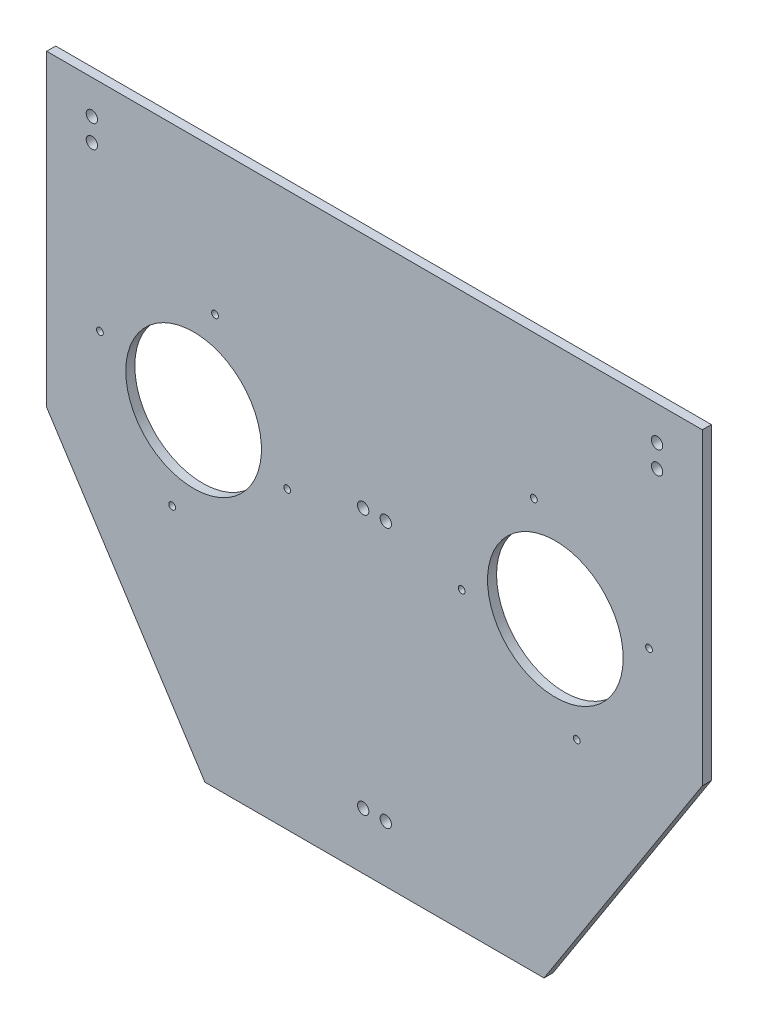
SolidWorks part; units mm, degrees
ref_plane "Front Plane" through (0, 0, 0) normal (0, 0, 1) x (1, 0, 0)
ref_plane "Top Plane" through (0, 0, 0) normal (0, 1, 0) x (1, 0, 0)
ref_plane "Right Plane" through (0, 0, 0) normal (1, 0, 0) x (0, 0, -1)
sketch "Sketch1" plane through (0, 0, 0) normal (0, 0, 1) x (1, 0, 0)
  line L0 (-125, 100) -> (125, 100) construction
  line L1 (-125, 0) -> (125, 0) construction
  line L2 (-145, -16.3871) -> (-75, -125)
  line L3 (-75, -125) -> (75, -125)
  line L4 (75, -125) -> (145, -16.3871)
  line L5 (-125, 105) -> (-125, 95) construction
  line L6 (0, -125) -> (0, 100) construction
  line L7 (-145, 120) -> (145, 120)
  line L8 (145, 120) -> (145, -16.3871)
  line L11 (-145, -16.3871) -> (-145, 120)
  line L12 (125, 105) -> (125, 95) construction
  line L13 (-5, -100) -> (5, -100) construction
  circle A0 centre (-125, 100) radius 12.5 construction
  circle A10 centre (-125, 0) radius 12.5 construction
  circle A11 centre (125, 0) radius 12.5 construction
  circle A12 centre (-125, 0) radius 17.5 construction
  circle A13 centre (-125, 100) radius 17.5 construction
  circle A25 centre (-125, 95) radius 2.5
  circle A26 centre (-125, 105) radius 2.5
  circle A27 centre (125, 95) radius 2.5
  circle A28 centre (125, 105) radius 2.5
  circle A29 centre (5, -100) radius 2.5
  circle A30 centre (-5, -100) radius 2.5
  point P12 (0, 100)
  point P15 (0, -100)
  point P27 (-145, -22.8851)
  point P29 (-145, -16.3871)
  point P45 (0, 120)
  dimension "D1" = 25
  dimension "D2" = 5
  dimension "D4" = 100
  dimension "D6" = 5
  dimension "D11" = 20
  dimension "D12" = 20
  dimension "D7" = 10
  dimension "D8" = 250
  dimension "D3" = 25
  dimension "D5" = 100
  dimension "D9" = 150
extrude "Boss-Extrude1" add sketch "Sketch1" along normal blind 4
sketch "Sketch2" plane through (0, 0, 4) normal (0, 0, 1) x (1, 0, 0)
  line L0 (121.4264, 24.4924) -> (38.5736, 5.5076) construction
  line L1 (89.4924, -26.4264) -> (70.5076, 56.4264) construction
  line L2 (0, 0) -> (0, 96.4486) construction
  line L3 (145, 120) -> (-145, 120) construction
  line L4 (-145, 120) -> (-145, -16.3871) construction
  line L5 (-80, 15) -> (80, 15) construction
  line L6 (-5, 15) -> (5, 15) construction
  circle A0 centre (80, 15) radius 42.5 construction
  circle A1 centre (38.5736, 5.5076) radius 1.5
  circle A2 centre (70.5076, 56.4264) radius 1.5
  circle A3 centre (121.4264, 24.4924) radius 1.5
  circle A4 centre (89.4924, -26.4264) radius 1.5
  circle A5 centre (80, 15) radius 30
  circle A6 centre (-38.5736, 5.5076) radius 1.5
  circle A7 centre (-70.5076, 56.4264) radius 1.5
  circle A8 centre (-89.4924, -26.4264) radius 1.5
  circle A9 centre (-121.4264, 24.4924) radius 1.5
  circle A10 centre (-80, 15) radius 42.5 construction
  circle A11 centre (-80, 15) radius 30
  circle A12 centre (-80, 15) radius 47.5 construction
  circle A15 centre (-5, 15) radius 2.5
  circle A16 centre (5, 15) radius 2.5
  point P6 (80, 15)
  point P27 (-80, 15)
  point P30 (0, 15)
  dimension "D1" = 85
  dimension "D2" = 3
  dimension "D3" = 60
  dimension "D4" = 95
  dimension "D5" = 5
  dimension "D6" = 105
  dimension "D7" = 65
  dimension "D8" = 10
extrude "Cut-Extrude1" cut sketch "Sketch2" against normal blind 10
equation "\"D1@Sketch1\" = \"cf_tube_outer_diameter\""
equation "\"mid_plate_mid_to_top\" = 100mm"
equation "\"mid_plate_mid_to_bottom\" = 100mm"
equation "\"mid_plate_horizontal_spacing\" = 250mm"
equation "\"cf_tube_outer_diameter\" = 25mm"
equation "\"D4@Sketch1\"=\"mid_plate_mid_to_top\""
equation "\"cf_tube_inner_diameter\" = 21mm"
equation "\"mid_tube_length\" = 500mm"
equation "\"cf_plate_thickness\" = 4mm"
equation "\"D1@Boss-Extrude1\"=\"cf_plate_thickness\""
equation "\"D8@Sketch1\"=\"mid_plate_horizontal_spacing\""
equation "\"D5@Sketch1\"=\"mid_plate_mid_to_bottom\""
equation "\"mid_plate_bottom_width\"= 150mm"
equation "\"D9@Sketch1\"=\"mid_plate_bottom_width\""
